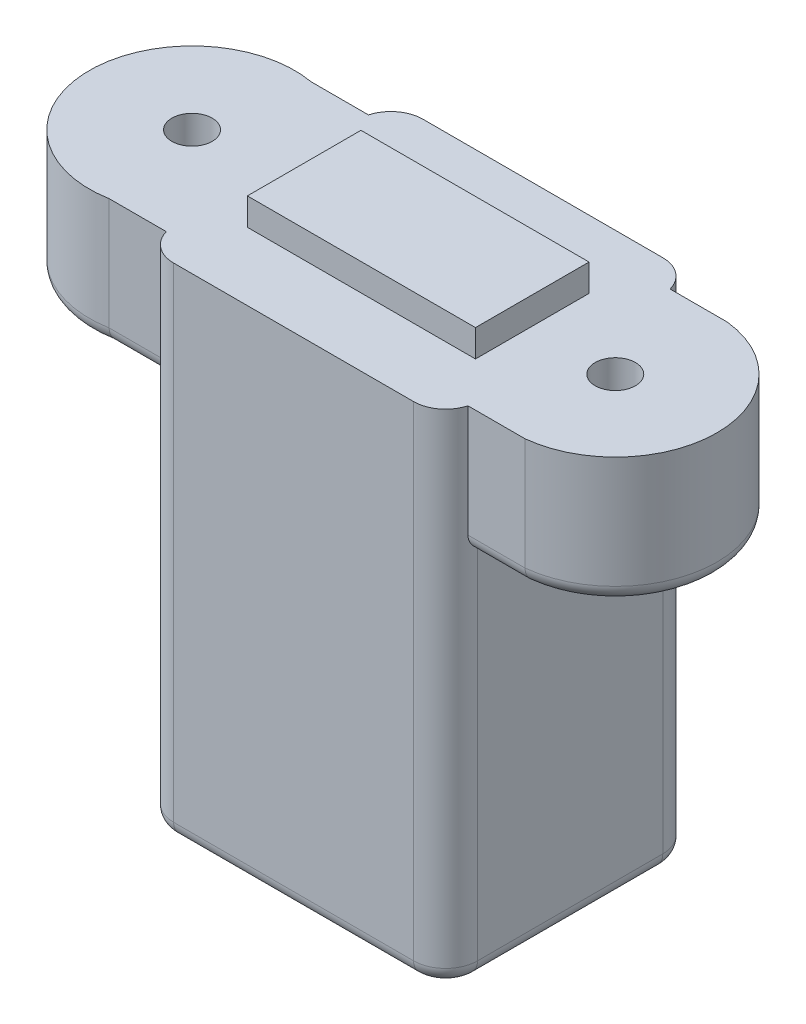
SolidWorks part; units mm, degrees
ref_plane "Front" through (0, 0, 0) normal (0, 0, 1) x (1, 0, 0)
ref_plane "Top" through (0, 0, 0) normal (0, 1, 0) x (1, 0, 0)
ref_plane "Right" through (0, 0, 0) normal (1, 0, 0) x (0, 0, -1)
sketch "Sketch1" plane through (0, 0, 0) normal (0, 1, 0) x (1, 0, 0)
  line L1 (8.255, -4.0132) -> (-8.255, -4.0132)
  line L3 (8.255, 4.0132) -> (-8.255, 4.0132)
  line L5 (8.255, -4.0132) -> (-8.255, 4.0132) construction
  line L6 (8.255, 4.0132) -> (-8.255, -4.0132) construction
  arc A0 (-8.255, 4.0132) -> (-8.255, -4.0132) centre (-8.979, 0) ccw
  arc A1 (8.255, 4.0132) -> (8.255, -4.0132) centre (7.824, 0) cw
  point P0 (0, 0)
  point P2 (0, 0)
  point P7 (0, 0)
  dimension "D1" = 8.0264
  dimension "D2" = 16.51
extrude "Boss-Extrude1" add sketch "Sketch1" along normal blind 5.08 contours L3 A0 L1 A1
ref_axis "Axis1" through (-8.979, 5.08, 0) along (0, -1, 0)
ref_axis "Axis2" through (7.824, 5.08, 0) along (0, -1, 0)
hole_wizard "M2x0.4 Tapped Hole1" positions "Sketch6" profile "Sketch7" tap size "M2x0.4" standard "ANSI Metric" end condition through all
sketch "Sketch6" plane through (0, 5.08, 0) normal (0, 1, 0) x (1, 0, 0)
  point P0 (-8.979, 0)
  point P2 (7.824, 0)
sketch "Sketch7" plane through (-8.979, 5.08, 0) normal (1, 0, 0) x (0, 0, 1)
  line L0 (0, 0) -> (0, 5.08)
  line L1 (0, 5.08) -> (0.8, 5.08)
  line L2 (0.8, 5.08) -> (0.8, 0)
  line L5 (0.8, 0) -> (0, 0)
  line L11 (0, -6.35) -> (0, 107.95) construction
  dimension "Thru Tap Drill Dia." = 1.6
  dimension "Thru Tap Drill Depth" = 5.08
cosmetic thread "Hole Thread1" parameters "D2"=2
cosmetic thread "Hole Thread2" parameters "D2"=2
sketch "Sketch8" plane through (0, 5.08, 0) normal (0, 1, 0) x (1, 0, 0)
  line L1 (6.0325, -4.9466) -> (-6.0325, -4.9466)
  line L2 (6.0325, -4.9466) -> (6.0325, 4.9467)
  line L3 (6.0325, 4.9467) -> (-6.0325, 4.9466)
  line L4 (-6.0325, -4.9466) -> (-6.0325, 4.9466)
  line L5 (6.0325, -4.9466) -> (-6.0325, 4.9466) construction
  line L6 (6.0325, 4.9467) -> (-6.0325, -4.9466) construction
  point P0 (0, 0)
  dimension "D1" = 12.065
  dimension "D2" = 9.8933
extrude "Boss-Extrude2" add sketch "Sketch8" against normal blind 19.8628
fillet "Fillet1" radius 1.27 4 edges at (-6.0325, -4.8514, 4.9466) (6.0325, -4.8514, 4.9466) (-6.0325, -4.8514, -4.9466) (6.0325, -4.8514, -4.9467)
fillet "Fillet2" radius 0.635 6 edges at (-7.121, 0, 4.0132) (-13.057, 0, 0) (-7.121, 0, -4.0132) (7.121, 0, -4.0132) (7.121, 0, 4.0132) (11.8603, 0, 0)
fillet "Fillet3" radius 0.635 8 edges at (5.6605, -14.7828, 4.5747) (6.0325, -14.7828, 0) (5.6605, -14.7828, -4.5747) (0, -14.7828, -4.9467) (-5.6605, -14.7828, -4.5747) (-6.0325, -14.7828, 0) (-5.6605, -14.7828, 4.5747) (0, -14.7828, 4.9466)
sketch "Sketch9" plane through (0, 5.08, 0) normal (0, 1, 0) x (1, 0, 0)
  line L0 (4.7625, 4.9467) -> (-4.7625, 4.9466) construction
  line L1 (-4.5276, -2.2543) -> (4.5275, -2.2543)
  line L2 (-4.5276, -2.2543) -> (-4.5276, 2.2542)
  line L3 (-4.5276, 2.2542) -> (4.5275, 2.2542)
  line L4 (4.5275, -2.2543) -> (4.5275, 2.2542)
  line L5 (-4.5276, -2.2543) -> (4.5275, 2.2542) construction
  line L6 (-4.5276, 2.2542) -> (4.5275, -2.2543) construction
  arc A0 (-8.255, 4.0132) -> (-8.255, -4.0132) centre (-8.979, 0) ccw construction
  point P0 (0, 0)
  point P7 (0, 4.9467)
  point P11 (-13.057, 0)
  dimension "D1" = 9.0551
  dimension "D2" = 4.5085
extrude "Boss-Extrude3" add sketch "Sketch9" along normal blind 1.0795
